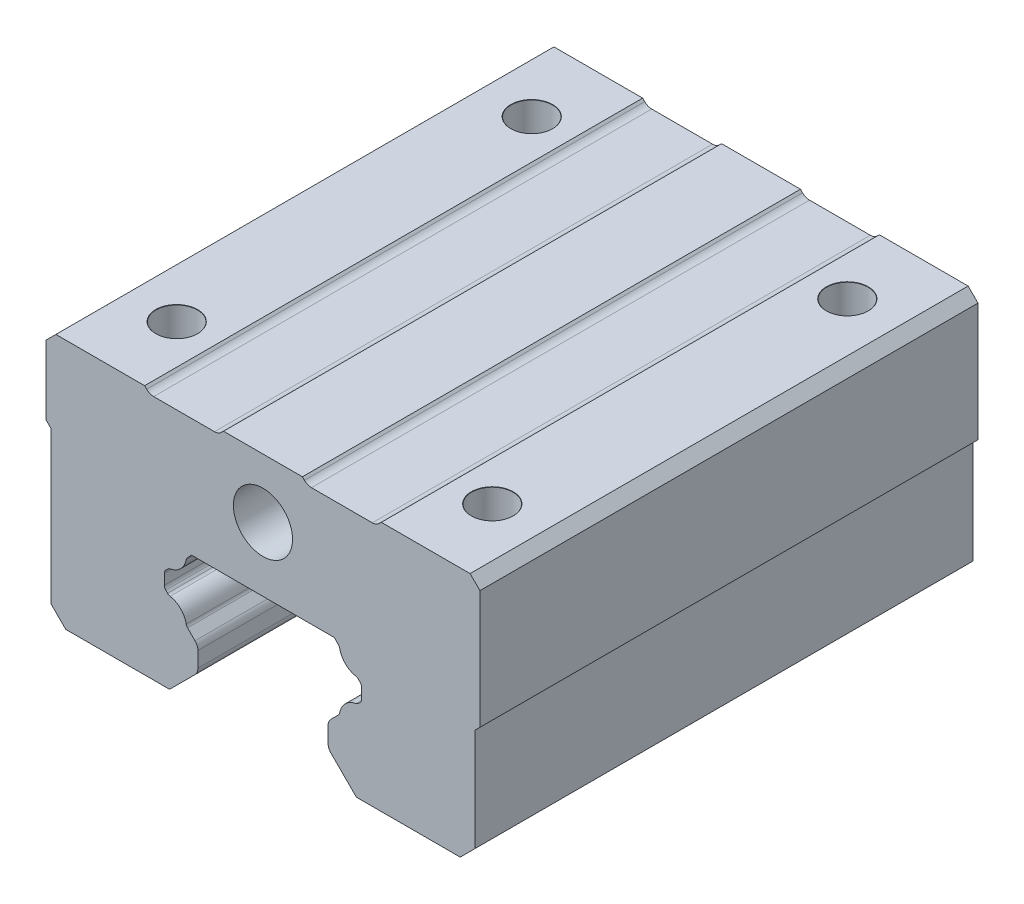
SolidWorks part; units mm, degrees
material "1060 Alloy"
ref_plane "Front Plane" through (0, 0, 0) normal (0, 0, 1) x (1, 0, 0)
ref_plane "Top Plane" through (0, 0, 0) normal (0, 1, 0) x (1, 0, 0)
ref_plane "Right Plane" through (0, 0, 0) normal (1, 0, 0) x (0, 0, -1)
sketch "Sketch2" plane through (0, 0, 0) normal (0, 0, 1) x (1, 0, 0)
  line L0 (-7.2307, 12.9) -> (7.2307, 12.9)
  line L1 (-7.6477, 12.483) -> (-7.2307, 12.9)
  line L2 (-9.8536, 10.2772) -> (-9.6633, 10.4674)
  line L3 (-10, 8.8664) -> (-10, 9.9236)
  line L4 (-9.6753, 8.3346) -> (-9.8536, 8.5128)
  line L5 (-6.8929, 5.5522) -> (-7.6454, 6.3047)
  line L6 (-6.6, 3.2849) -> (-6.6, 4.8451)
  line L7 (-9.4707, 0) -> (-6.8929, 2.5778)
  line L13 (6.8929, 2.5778) -> (9.4707, 0)
  line L14 (6.6, 4.8451) -> (6.6, 3.2849)
  line L15 (7.6454, 6.3047) -> (6.8929, 5.5522)
  line L16 (9.8536, 8.5128) -> (9.6753, 8.3346)
  line L17 (10, 9.9236) -> (10, 8.8664)
  line L18 (9.6633, 10.4674) -> (9.8536, 10.2772)
  line L19 (7.2307, 12.9) -> (7.6477, 12.483)
  line L22 (0, -1000) -> (0, 49000) construction
  line L37 (-1000, 0) -> (49000, 0) construction
  line L73 (22, 12.3998) -> (21.5001, 11.9)
  line L74 (22, 24.4) -> (22, 12.3998)
  line L75 (20.9999, 25.4) -> (22, 24.4)
  line L76 (11.9999, 25.4) -> (20.9999, 25.4)
  line L77 (11.7928, 25.1929) -> (11.9999, 25.4)
  line L78 (4.9141, 24.9) -> (11.0857, 24.9)
  line L79 (4.0001, 25.4) -> (4.207, 25.1929)
  line L80 (-3.9999, 25.4) -> (4.0001, 25.4)
  line L81 (-4.207, 25.1929) -> (-3.9999, 25.4)
  line L82 (-11.0857, 24.9) -> (-4.9141, 24.9)
  line L83 (-11.9999, 25.4) -> (-11.7928, 25.1929)
  line L84 (-20.9999, 25.4) -> (-11.9999, 25.4)
  line L85 (-22, 24.4) -> (-20.9999, 25.4)
  line L86 (-22, 17.4) -> (-22, 24.4)
  line L87 (-21.5001, 16.9002) -> (-22, 17.4)
  line L92 (19.9999, 0) -> (9.4707, 0)
  line L93 (21.5001, 1.5) -> (19.9999, 0)
  line L94 (21.5001, 11.9) -> (21.5001, 1.5)
  line L98 (-21.5001, 1.5) -> (-21.5001, 16.9002)
  line L99 (-19.9999, 0) -> (-21.5001, 1.5)
  line L100 (-9.4707, 0) -> (-19.9999, 0)
  line L983 (18.7501, 9.9) -> (18.7501, 14.9) construction
  line L984 (16.2501, 12.4) -> (21.2501, 12.4) construction
  line L985 (-18.7501, 9.9) -> (-18.7501, 14.9) construction
  line L986 (-21.2499, 12.4) -> (-16.2499, 12.4) construction
  arc A0 (-7.6477, 12.483) -> (-7.7854, 12.2224) centre (-7.2941, 12.1295) ccw
  arc A1 (-9.4027, 10.6051) -> (-7.7854, 12.2224) centre (-9.78, 12.5997) ccw
  arc A2 (-9.4027, 10.6051) -> (-9.6633, 10.4674) centre (-9.3098, 10.1138) ccw
  arc A3 (-9.8536, 10.2772) -> (-10, 9.9236) centre (-9.5, 9.9236) ccw
  arc A4 (-10, 8.8664) -> (-9.8536, 8.5128) centre (-9.5, 8.8664) ccw
  arc A5 (-9.6753, 8.3346) -> (-9.4124, 8.1964) centre (-9.3218, 8.6882) ccw
  arc A6 (11.0857, 24.9) -> (11.7928, 25.1929) centre (11.0857, 25.9) ccw
  arc A7 (-7.7836, 6.5677) -> (-9.4124, 8.1964) centre (-9.78, 6.2) ccw
  arc A8 (4.207, 25.1929) -> (4.9141, 24.9) centre (4.9141, 25.9) ccw
  arc A9 (-7.7836, 6.5677) -> (-7.6454, 6.3047) centre (-7.2919, 6.6583) ccw
  arc A10 (-6.6, 4.8451) -> (-6.8929, 5.5522) centre (-7.6, 4.8451) ccw
  arc A11 (-6.8929, 2.5778) -> (-6.6, 3.2849) centre (-7.6, 3.2849) ccw
  arc A14 (6.6, 3.2849) -> (6.8929, 2.5778) centre (7.6, 3.2849) ccw
  arc A15 (6.8929, 5.5522) -> (6.6, 4.8451) centre (7.6, 4.8451) ccw
  arc A16 (7.6454, 6.3047) -> (7.7836, 6.5677) centre (7.2919, 6.6583) ccw
  arc A17 (9.4124, 8.1964) -> (9.6753, 8.3346) centre (9.3218, 8.6882) ccw
  arc A18 (9.4124, 8.1964) -> (7.7836, 6.5677) centre (9.78, 6.2) ccw
  arc A19 (9.8536, 8.5128) -> (10, 8.8664) centre (9.5, 8.8664) ccw
  arc A20 (10, 9.9236) -> (9.8536, 10.2772) centre (9.5, 9.9236) ccw
  arc A21 (9.6633, 10.4674) -> (9.4027, 10.6051) centre (9.3098, 10.1138) ccw
  arc A22 (7.7854, 12.2224) -> (9.4027, 10.6051) centre (9.78, 12.5997) ccw
  arc A23 (7.7854, 12.2224) -> (7.6477, 12.483) centre (7.2941, 12.1295) ccw
  arc A30 (-4.9141, 24.9) -> (-4.207, 25.1929) centre (-4.9141, 25.9) ccw
  arc A31 (-11.7928, 25.1929) -> (-11.0857, 24.9) centre (-11.0857, 25.9) ccw
  dimension "D10" = 12.9
  dimension "D8" = 1.5
  dimension "D1" = 25.4
  dimension "D12" = 1
  dimension "D3" = 44
  dimension "D4" = 1
  dimension "D5" = 1.0001
  dimension "D6" = 0.4999
  dimension "D7" = 0.4998
  dimension "D9" = 1.5002
  dimension "D11" = 0.5
  dimension "D13" = 9
  dimension "D14" = 8
  dimension "D15" = 13.2
  dimension "D17" = 20
  dimension "D20" = 12.4
  dimension "D21" = 2.75
  dimension "D22" = 2.75
extrude "Block" add sketch "Sketch2" along normal mid plane 50.5
hole_wizard "Tap Drill for M5x0.8 Tap1" positions "Sketch6" profile "Sketch5" hole size "M5x0.8" standard "ANSI Metric"
sketch "Sketch6" plane through (0, 25.4, 0) normal (0, 1, 0) x (1, 0, 0)
  line L0 (-1000, 0) -> (49000, 0) construction
  line L1 (0, -1000) -> (0, 49000) construction
  point P0 (16, 18)
  point P2 (-16, 18)
  point P4 (16, -18)
  point P6 (-16, -18)
  dimension "D1" = 32
  dimension "D2" = 36
cosmetic thread "Cosmetic Thread1" parameters "D1"=6, "D2"=5
cosmetic thread "Cosmetic Thread2" parameters "D1"=6, "D2"=5
cosmetic thread "Cosmetic Thread3" parameters "D1"=6, "D2"=5
cosmetic thread "Cosmetic Thread4" parameters "D1"=6, "D2"=5
sketch "Sketch5" plane through (16, 25.4, -18) normal (1, 0, 0) x (0, 0, 1)
  line L0 (0, 0) -> (0, 8.5932)
  line L1 (0, 8.5932) -> (2.1, 7.5)
  line L2 (2.1, 7.5) -> (2.1, 0.025)
  line L3 (2.1, 0.025) -> (2.125, 0)
  line L5 (2.125, 0) -> (0, 0)
  line L6 (-2.1, 0.025) -> (-2.125, 0) construction
  line L10 (0, 8.5932) -> (-2.1, 7.5) construction
  line L11 (0, -6.35) -> (0, 107.95) construction
  dimension "Hole Dia." = 4.2
  dimension "Hole Depth" = 7.5
  dimension "Near C'Sink Dia." = 4.25
  dimension "Near C'Sink Angle" = 90
  dimension "Drill Angle" = 125
hole_wizard "Ø6.0 (6) Diameter Hole1" positions "Sketch9" profile "Sketch8" hole size "Ø6.0" standard "ANSI Metric" end condition through all
sketch "Sketch9" plane through (0, 0, -25.25) normal (0, 0, -1) x (-1, 0, 0)
  line L1 (11.9999, 25.4) -> (20.9999, 25.4) construction
  line L2 (0, -1000) -> (0, 49000) construction
  point P0 (0, 19.4)
  dimension "D1" = 6
sketch "Sketch8" plane through (0, 19.4, -25.25) normal (1, 0, 0) x (0, 1, 0)
  line L0 (0, 0) -> (0, 50.5)
  line L1 (0, 50.5) -> (3, 50.5)
  line L2 (3, 50.5) -> (3, 0)
  line L5 (3, 0) -> (0, 0)
  line L11 (0, -6.35) -> (0, 107.95) construction
  dimension "Thru Hole Dia." = 6
  dimension "Thru Hole Depth" = 50.5
